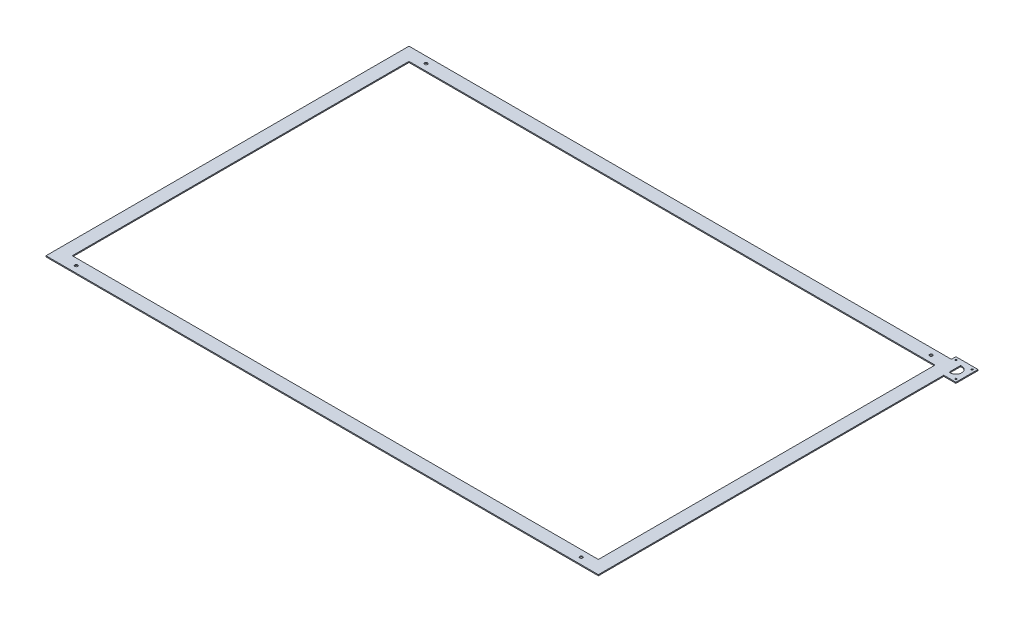
SolidWorks part; units mm, degrees
ref_plane "Plan de face" through (0, 0, 0) normal (0, 0, 1) x (1, 0, 0)
ref_plane "Plan de dessus" through (0, 0, 0) normal (0, 1, 0) x (1, 0, 0)
ref_plane "Plan de droite" through (0, 0, 0) normal (1, 0, 0) x (0, 0, -1)
sketch "Esquisse1" plane through (0, 0, 0) normal (0, 1, 0) x (1, 0, 0)
  line L0 (-204.0391, 511.3012) -> (795.9609, 511.3012)
  line L1 (-204.0391, 536.3012) -> (795.9609, 536.3012)
  line L2 (-204.0391, 536.3012) -> (-204.0391, -153.6988)
  line L3 (-204.0391, -153.6988) -> (795.9609, -153.6988)
  line L4 (795.9609, 536.3012) -> (795.9609, -153.6988)
  line L5 (-204.0391, -128.6988) -> (795.9609, -128.6988)
  line L6 (-204.0391, -153.6988) -> (-229.0391, -153.6988)
  line L7 (-229.0391, -153.6988) -> (-229.0391, 536.3012)
  line L8 (-229.0391, 536.3012) -> (-204.0391, 536.3012)
  line L9 (795.9609, 536.3012) -> (820.9609, 536.3012)
  line L10 (820.9609, 536.3012) -> (820.9609, -153.6988)
  line L11 (820.9609, -153.6988) -> (795.9609, -153.6988)
  dimension "D1" = 25
  dimension "D2" = 25
  dimension "D3" = 690
  dimension "D4" = 1000
  dimension "D5" = 25
  dimension "D6" = 25
extrude "Boss.-Extru.1" add sketch "Esquisse1" along normal blind 2 contours L5 L2 L3 L4 | L4 L1 L2 L0 | L8 L7 L6 L2 | L11 L10 L9 L4 region at (295.9609, 0, -523.8012) region at (-216.5391, 0, -191.3012) region at (808.4609, 0, -191.3012) region at (295.9609, 0, 141.1988)
sketch "Esquisse2" plane through (0, 2, 0) normal (0, 1, 0) x (1, 0, 0)
  line L1 (795.9609, -128.6988) -> (795.9609, 511.3012) construction
  line L2 (795.9609, -128.6988) -> (795.9609, 511.3012) construction
  line L3 (-204.0391, -128.6988) -> (-204.0391, 511.3012) construction
  line L4 (-204.0391, -128.6988) -> (-204.0391, 511.3012) construction
  line L5 (-229.0391, 536.3012) -> (820.9609, 536.3012) construction
  line L6 (-204.0391, -128.6988) -> (795.9609, -128.6988) construction
  circle A0 centre (-184.0391, -141.1988) radius 2.75
  circle A1 centre (775.9609, -141.1988) radius 2.75
  circle A2 centre (775.9609, 523.8012) radius 2.75
  circle A3 centre (-184.0391, 523.8012) radius 2.75
  point P20 (0, 0)
  dimension "D1" = 5.5
  dimension "D2" = 5.5
  dimension "D3" = 5.5
  dimension "D4" = 5.5
  dimension "D5" = 20
  dimension "D6" = 20
  dimension "D7" = 20
  dimension "D8" = 20
  dimension "D9" = 12.5
  dimension "D10" = 12.5
  dimension "D11" = 12.5
  dimension "D12" = 12.5
extrude "Enlèv. mat.-Extru.1" cut sketch "Esquisse2" against normal blind 2
sketch "Esquisse3" plane through (0, 2, 0) normal (0, 1, 0) x (1, 0, 0)
  line L1 (802.0028, 544.89) -> (844.0028, 544.89)
  line L2 (802.0028, 544.89) -> (802.0028, 502.89)
  line L3 (802.0028, 502.89) -> (844.0028, 502.89)
  line L4 (844.0028, 544.89) -> (844.0028, 502.89)
  line L5 (838.5028, 508.39) -> (807.5028, 508.39)
  line L6 (838.5028, 508.39) -> (838.5028, 539.39)
  line L7 (838.5028, 539.39) -> (807.5028, 539.39)
  line L8 (807.5028, 508.39) -> (807.5028, 539.39)
  circle A0 centre (807.5028, 508.39) radius 1.5
  circle A1 centre (807.5028, 539.39) radius 1.5
  circle A2 centre (838.5028, 539.39) radius 1.5
  circle A3 centre (838.5028, 508.39) radius 1.5
  circle A4 centre (823.0028, 523.89) radius 11
  line M20 (820.9609, 536.3012) -> (-229.0391, 536.3012)
  line M23 (820.9609, -153.6988) -> (820.9609, 536.3012)
  dimension "D7" = 3
  dimension "D8" = 3
  dimension "D9" = 3
  dimension "D10" = 3
  dimension "D13" = 22
  dimension "D1" = 42
  dimension "D2" = 42
  dimension "D3" = 31
  dimension "D4" = 31
  dimension "D5" = 5.5
  dimension "D6" = 5.5
  dimension "D11" = 21
  dimension "D12" = 21
extrude "Boss.-Extru.2" add sketch "Esquisse3" against normal blind 2 contours A4 L5 A3 L6 A2 L7 A1 L8 M23 M20 | A3 L5 L3 L4 L1 L2 L8 A1 L7 A2 L6 M23 M20 region at (823.0028, 2, -544.296) region at (807.9412, 2, -537.0956)
